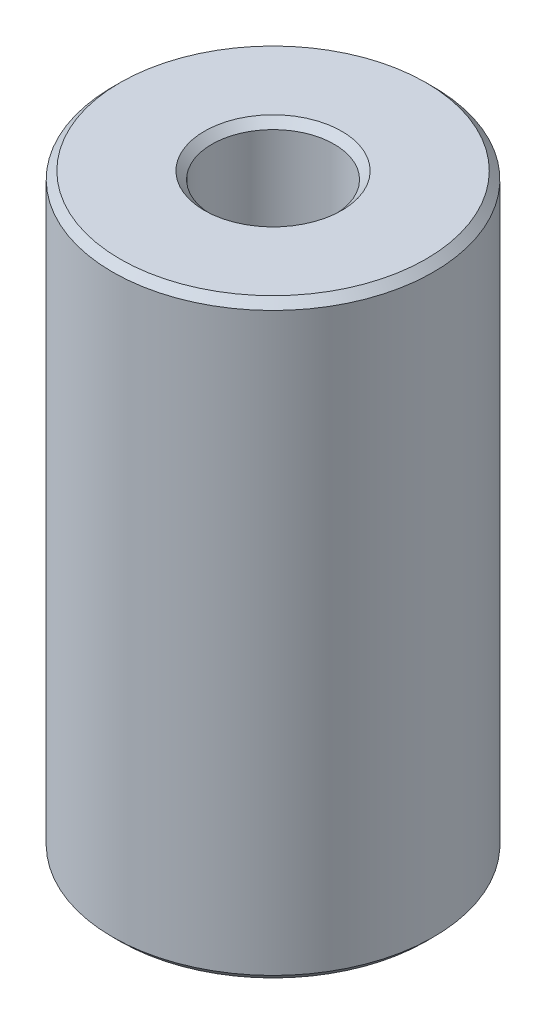
SolidWorks part; units mm, degrees
ref_plane "Front Plane" through (0, 0, 0) normal (0, 0, 1) x (1, 0, 0)
ref_plane "Top Plane" through (0, 0, 0) normal (0, 1, 0) x (1, 0, 0)
ref_plane "Right Plane" through (0, 0, 0) normal (1, 0, 0) x (0, 0, -1)
sketch "Sketch1" plane through (0, 0, 0) normal (0, 1, 0) x (1, 0, 0)
  circle A0 centre (0, 0) radius 40
  dimension "SLEEVE_OD" = 80
extrude "Boss-Extrude1" add sketch "Sketch1" along normal blind 147.3453
sketch "Sketch2" plane through (0, 0, 0) normal (0, 1, 0) x (1, 0, 0)
  circle A0 centre (0, 0) radius 15.2562
  dimension "BORE_D" = 30.5124
extrude "Cut-Extrude1" cut sketch "Sketch2" along normal through all
chamfer "Chamfer1" distance 1.8725 angle 45 4 edges at (0, 147.3453, 15.2562) (0, 0, 15.2562) (0, 0, 40) (0, 147.3453, 40)
